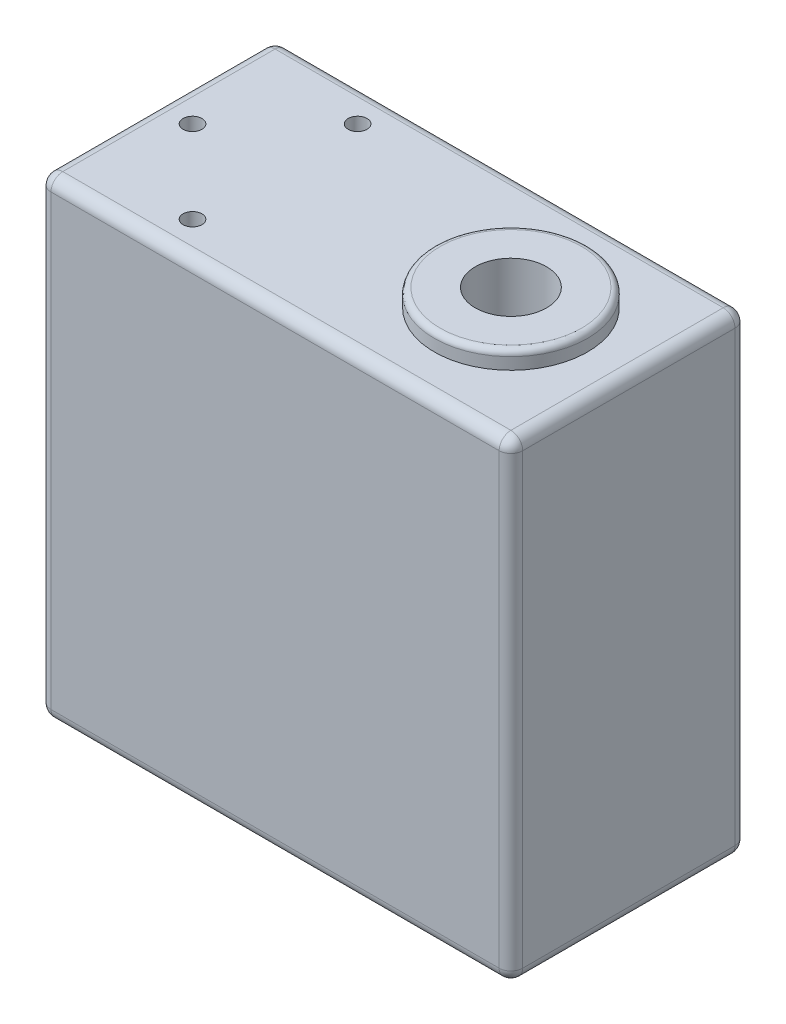
SolidWorks part; units mm, degrees
ref_plane "前视基准面" through (0, 0, 0) normal (0, 0, 1) x (1, 0, 0)
ref_plane "上视基准面" through (0, 0, 0) normal (0, 1, 0) x (1, 0, 0)
ref_plane "右视基准面" through (0, 0, 0) normal (1, 0, 0) x (0, 0, -1)
sketch "草图1" plane through (0, 0, 0) normal (0, 0, 1) x (1, 0, 0)
  line L1 (-20, 20) -> (20, 20)
  line L2 (-20, 20) -> (-20, -20)
  line L3 (-20, -20) -> (20, -20)
  line L4 (20, 20) -> (20, -20)
  line L5 (-20, 20) -> (20, -20) construction
  line L6 (-20, -20) -> (20, 20) construction
  point P0 (0, 0)
  dimension "D1" = 40
  dimension "D2" = 40
extrude "凸台-拉伸1" add sketch "草图1" along normal mid plane 20
fillet "圆角1" radius 1 12 edges at (-20, 20, 0) (-20, -20, 0) (20, -20, 0) (20, 20, 0) (0, 20, -10) (-20, 0, -10) (0, -20, -10) (20, 0, -10) (0, -20, 10) (-20, 0, 10) (0, 20, 10) (20, 0, 10)
sketch "草图2" plane through (0, -20, 0) normal (0, -1, 0) x (1, 0, 0)
  line L0 (-28.9102, 0) -> (27.7907, 0) construction
  circle A0 centre (10, 0) radius 6.5
  circle A1 centre (10, 0) radius 3.75
  circle A2 centre (10, 0) radius 3
  circle A3 centre (10, 0) radius 1.75
  dimension "D1" = 10
  dimension "D2" = 13
  dimension "D3" = 7.5
  dimension "D4" = 6
  dimension "D5" = 3.5
sketch "草图5" plane through (0, -20, 0) normal (0, -1, 0) x (-1, 0, 0)
  line L0 (29.1816, 0) -> (-28.5273, 0) construction
  line L1 (10, -14.9506) -> (10, 14.9506) construction
  line L2 (20, 9) -> (20, -9) construction
  circle A0 centre (17.5, -7.5) radius 0.8
  circle A1 centre (2.5, -7.5) radius 0.8
  circle A2 centre (2.5, 7.5) radius 0.8
  circle A3 centre (17.5, 7.5) radius 0.8
  point P5 (10, 0)
  point P19 (10, 0)
  dimension "D2" = 1.6
  dimension "D1" = 10
  dimension "D3" = 7.5
  dimension "D4" = 7.5
  dimension "D5" = 4
extrude "切除-拉伸2" cut sketch "草图5" against normal blind 5
sketch "草图6" plane through (0, 20, 0) normal (0, 1, 0) x (1, 0, 0)
  line L0 (27.1316, 0) -> (-27.7214, 0) construction
  line L1 (-10, 14.6471) -> (-10, -14.6471) construction
  line L2 (-20, -9) -> (-20, 9) construction
  line L3 (-10, 0) -> (-10, 7) construction
  line L4 (-10, 0) -> (-17, 0) construction
  circle A0 centre (-10, 7) radius 0.8
  circle A1 centre (-17, 0) radius 0.8
  circle A2 centre (-10, -7) radius 0.8
  point P9 (-10, 0)
  dimension "D2" = 1.6
  dimension "D5" = 14
  dimension "D1" = 10
  dimension "D4" = 90
  dimension "D6" = 7
  dimension "D3" = 3
extrude "切除-拉伸3" cut sketch "草图6" against normal blind 5
extrude "凸台-拉伸2" add sketch "草图2" along normal blind 1.5 contours A0
extrude "凸台-拉伸3" add sketch "草图2<3>" along normal blind 1.8 contours A1
sketch "草图2<3>" plane through (0, -20, 0) normal (0, -1, 0) x (1, 0, 0) same geometry as "草图2"
extrude "凸台-拉伸4" add sketch "草图2<4>" along normal blind 5.7 contours A2
sketch "草图2<4>" plane through (0, -20, 0) normal (0, -1, 0) x (1, 0, 0) same geometry as "草图2"
extrude "切除-拉伸4" cut sketch "草图2<5>" against normal blind 7 from surface contours A3 starting at face at (10, -25.7, -3)
sketch "草图2<5>" plane through (0, -20, 0) normal (0, -1, 0) x (1, 0, 0) same geometry as "草图2"
fillet "圆角2" radius 0.5 1 edges at (10, -21.5, -6.5)
sketch "草图4" plane through (0, 20, 0) normal (0, 1, 0) x (1, 0, 0)
  line L0 (-26.7423, 0) -> (24.9215, 0) construction
  circle A0 centre (10, 0) radius 6.5
  circle A1 centre (10, 0) radius 3.025
  dimension "D1" = 13
  dimension "D3" = 6.05
  dimension "D2" = 10
extrude "凸台-拉伸5" add sketch "草图4" along normal blind 1.5 contours A0
extrude "切除-拉伸5" cut sketch "草图4<4>" against normal blind 7 from surface contours A1 starting at face at (10, 21.5, 6.5)
sketch "草图4<4>" plane through (0, 20, 0) normal (0, 1, 0) x (1, 0, 0) same geometry as "草图4"
fillet "圆角3" radius 0.5 1 edges at (10, 21.5, 6.5)
